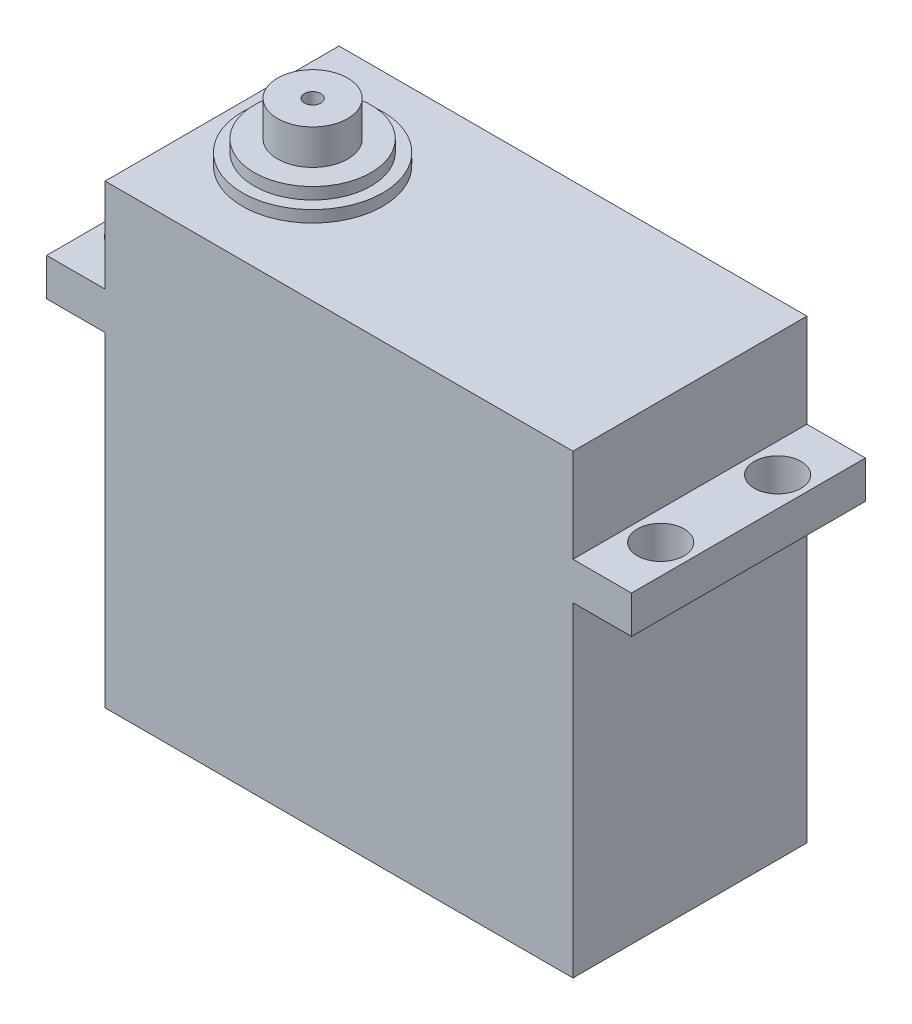
SolidWorks part; units mm, degrees
ref_plane "前视基准面" through (0, 0, 0) normal (0, 0, 1) x (1, 0, 0)
ref_plane "上视基准面" through (0, 0, 0) normal (0, 1, 0) x (1, 0, 0)
ref_plane "右视基准面" through (0, 0, 0) normal (1, 0, 0) x (0, 0, -1)
other "Configuration Table"
sketch "草图1" plane through (0, 0, 0) normal (0, 0, 1) x (1, 0, 0)
  line L1 (-32.988, 37.7943) -> (7.012, 37.7943)
  line L2 (-32.988, 37.7943) -> (-32.988, -1.2057)
  line L3 (-32.988, -1.2057) -> (7.012, -1.2057)
  line L4 (7.012, 37.7943) -> (7.012, -1.2057)
  line L5 (-12.988, -1.2057) -> (-12.988, 37.7943) construction
  line L6 (-32.988, 18.2943) -> (7.012, 18.2943) construction
  point P0 (-12.988, 18.2943)
  dimension "D1" = 40
  dimension "D2" = 39
extrude "凸台-拉伸1" add sketch "草图1" along normal blind 20
sketch "草图2" plane through (7.012, 0, 0) normal (1, 0, 0) x (0, 0, -1)
  line L0 (-20, -1.2057) -> (-20, 29.7943)
  line L1 (-20, -1.2057) -> (-20, 37.7943) construction
  line L2 (0, -1.2057) -> (0, 37.7943) construction
  line L3 (-20, 29.7943) -> (0, 29.7943)
  line L4 (-20, 29.7943) -> (-20, 26.5791)
  line L5 (-20, 26.5791) -> (0, 26.5791)
  line L6 (0, 29.7943) -> (0, 26.5791)
  dimension "D1" = 31
sketch "草图4" plane through (-32.988, 0, 0) normal (-1, 0, 0) x (0, 0, 1)
  line L1 (0, 29.7943) -> (20, 29.7943)
  line L2 (0, 29.7943) -> (0, 26.5791)
  line L3 (0, 26.5791) -> (20, 26.5791)
  line L4 (20, 29.7943) -> (20, 26.5791)
extrude "凸台-拉伸2" add sketch "草图4" along normal blind 5
sketch "草图5" plane through (7.012, 0, 0) normal (1, 0, 0) x (0, 0, -1)
  line L1 (-20, 29.7943) -> (0, 29.7943)
  line L2 (-20, 29.7943) -> (-20, 26.5791)
  line L3 (-20, 26.5791) -> (0, 26.5791)
  line L4 (0, 29.7943) -> (0, 26.5791)
extrude "凸台-拉伸3" add sketch "草图5" along normal blind 5
sketch "草图6" plane through (0, 29.7943, 0) normal (0, 1, 0) x (1, 0, 0)
sketch "草图7" plane through (0, 29.7943, 0) normal (0, 1, 0) x (1, 0, 0)
  line L2 (-37.988, -20) -> (-37.988, -14.7315)
  line L3 (-37.988, -20) -> (-37.988, 0) construction
  circle A0 centre (-35.488, -5.339) radius 2
  circle A1 centre (-35.488, -14.7315) radius 2
  dimension "D1" = 4
  dimension "D2" = 4
extrude "切除-拉伸2" cut sketch "草图7" against normal blind 3.2152 contours A0 | A1 region at (-35.488, 29.7943, 5.339) region at (-35.488, 29.7943, 14.7315)
sketch "草图8" plane through (0, 29.7943, 0) normal (0, 1, 0) x (1, 0, 0)
  circle A0 centre (9.512, -5) radius 2
  circle A1 centre (9.512, -15) radius 2
extrude "切除-拉伸3" cut sketch "草图8" against normal blind 3.2152
sketch "草图9" plane through (0, 37.7943, 0) normal (0, 1, 0) x (1, 0, 0)
  circle A0 centre (-25.245, -10) radius 6
extrude "凸台-拉伸7" add sketch "草图9" against normal through all and the other way blind 1
sketch "草图10" plane through (0, 38.7943, 0) normal (0, 1, 0) x (1, 0, 0)
  circle A0 centre (-25.245, -10) radius 5
extrude "凸台-拉伸9" add sketch "草图10" against normal through all and the other way blind 1
sketch "草图11" plane through (0, 39.7943, 0) normal (0, 1, 0) x (1, 0, 0)
  circle A0 centre (-25.245, -10) radius 3
extrude "凸台-拉伸10" add sketch "草图11" against normal through all and the other way blind 3
sketch "草图12" plane through (0, 42.7943, 0) normal (0, 1, 0) x (1, 0, 0)
  circle A0 centre (-25.245, -10) radius 0.7053
extrude "切除-拉伸4" cut sketch "草图12" against normal blind 40
